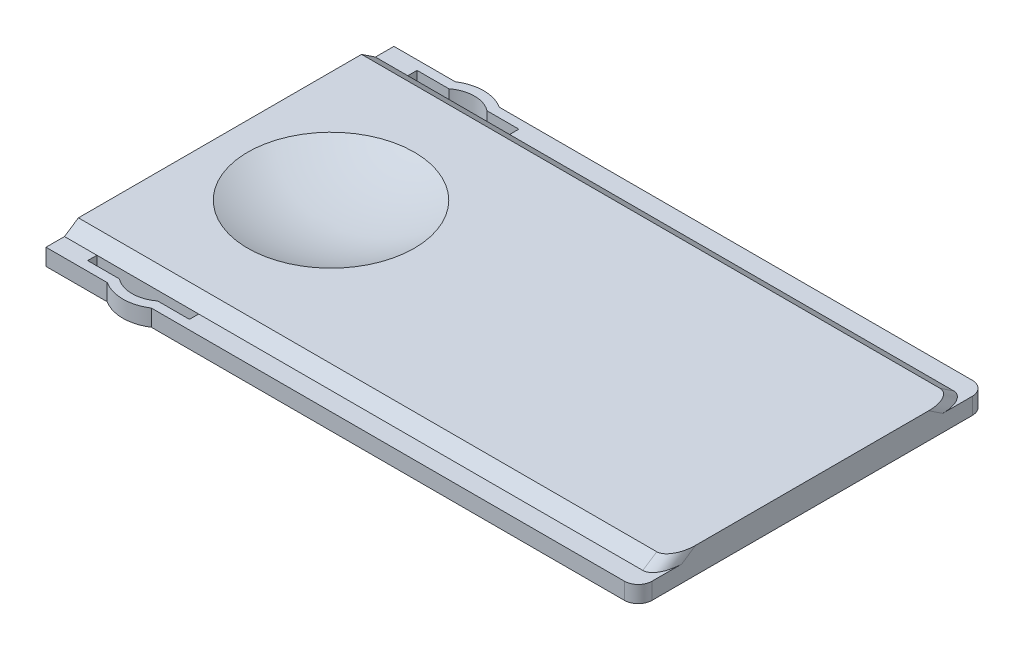
SolidWorks part; units mm, degrees
ref_plane "Front Plane" through (0, 0, 0) normal (0, 0, 1) x (1, 0, 0)
ref_plane "Top Plane" through (0, 0, 0) normal (0, 1, 0) x (1, 0, 0)
ref_plane "Right Plane" through (0, 0, 0) normal (1, 0, 0) x (0, 0, -1)
sketch "Sketch1" plane through (0, 0, 0) normal (1, 0, 0) x (0, 0, -1)
  line L0 (18.8, 0) -> (-18.8, 0)
  line L1 (-18.8, 0) -> (-18.8, 1.8)
  line L2 (-18.8, 1.8) -> (-16.8, 1.8)
  line L3 (-16.8, 1.8) -> (-15.3, 2.8)
  line L4 (-15.3, 2.8) -> (15.3, 2.8)
  line L5 (0, 2.8) -> (0, 0) construction
  line L6 (16.8, 1.8) -> (15.3, 2.8)
  line L7 (18.8, 1.8) -> (16.8, 1.8)
  line L8 (18.8, 0) -> (18.8, 1.8)
  point P11 (-15.6231, 3)
  dimension "D1" = 1.8
  dimension "D2" = 37.6
  dimension "D3" = 2.8
  dimension "D4" = 2
  dimension "D5" = 1.5
extrude "Boss-Extrude1" add sketch "Sketch1" along normal blind 64
sketch "Sketch2" plane through (0, 1.8, 0) normal (0, 1, 0) x (1, 0, 0)
  line L0 (0, 0) -> (64, 0) construction
  line L1 (64, 15.3) -> (64, -15.3) construction
  line L3 (0, 15.3) -> (0, -15.3) construction
  circle A0 centre (9, 15.1) radius 4.4
  circle A1 centre (9, -15.1) radius 4.4
  point P7 (9.5316, 19.7807)
  point P8 (9.6821, 15.6942)
  dimension "D1" = 8.8
  dimension "D2" = 15.1
  dimension "D3" = 9
extrude "Boss-Extrude-Latch" add sketch "Sketch2" against normal up to surface (1.8 mm away) up to face at (32, 0, 0)
sketch "Sketch3" plane through (0, 1.8, 0) normal (0, 1, 0) x (1, 0, 0)
  line L1 (3.5, 17.8) -> (6.9336, 17.8)
  line L2 (3.5, 17.8) -> (3.5, 16.8)
  line L3 (3.5, 16.8) -> (14.5, 16.8)
  line L4 (14.5, 17.8) -> (14.5, 16.8)
  line L5 (3.5, 17.8) -> (14.5, 16.8) construction
  line L6 (3.5, 16.8) -> (14.5, 17.8) construction
  line L7 (9, 19.5) -> (9, 17.3) construction
  line L9 (0, 18.8) -> (0, 16.8) construction
  line L10 (64, 16.8) -> (0, 16.8) construction
  line L11 (0, 0) -> (64, 0) construction
  line L12 (64, 15.3) -> (64, -15.3) construction
  line L13 (14.5, -17.8) -> (14.5, -16.8)
  line L14 (11.0664, -17.8) -> (14.5, -17.8)
  line L15 (3.5, -17.8) -> (6.9336, -17.8)
  line L16 (3.5, -17.8) -> (3.5, -16.8)
  line L17 (11.0664, 17.8) -> (14.5, 17.8)
  line L18 (6.6188, 18.8) -> (0, 18.8) construction
  line L19 (3.5, -16.8) -> (14.5, -16.8)
  arc A0 (11.3812, 18.8) -> (6.6188, 18.8) centre (9, 15.1) ccw construction
  arc A2 (11.0664, -17.8) -> (6.9336, -17.8) centre (9, -15.1) cw
  arc A3 (10.84, 17.9591) -> (7.16, 17.9591) centre (9, 15.1) ccw
  arc A4 (11.0664, 17.8) -> (6.9336, 17.8) centre (9, 15.1) ccw
  point P0 (9, 17.3)
  point P25 (11.0557, 17.8)
  point P27 (6.923, 17.8)
  point P32 (11.0774, 17.8)
  dimension "D5" = 1
  dimension "D1" = 1
  dimension "D2" = 1
  dimension "D3" = 11
  dimension "D4" = 3.5
extrude "Cut-Extrude1" cut sketch "Sketch3" against normal through all
sketch "Sketch4" plane through (0, 0, 0) normal (0, 0, 1) x (1, 0, 0)
  line L0 (12, 43.3) -> (12, 0.8)
  line L2 (3, 2.8) -> (12, 2.8) construction
  line L3 (64, 2.8) -> (0, 2.8) construction
  arc A0 (12, 0.8) -> (12, 43.3) centre (12, 22.05) cw
  dimension "D1" = 0.8
  dimension "D2" = 9
  dimension "D3" = 12
revolve "Cut-Revolve1" cut sketch "Sketch4" angle 360 about L0
fillet "Fillet1" radius 1.5 4 edges at (64, 0.9, 18.8) (64, 2.3, 16.05) (64, 2.3, -16.05) (64, 0.9, -18.8)
